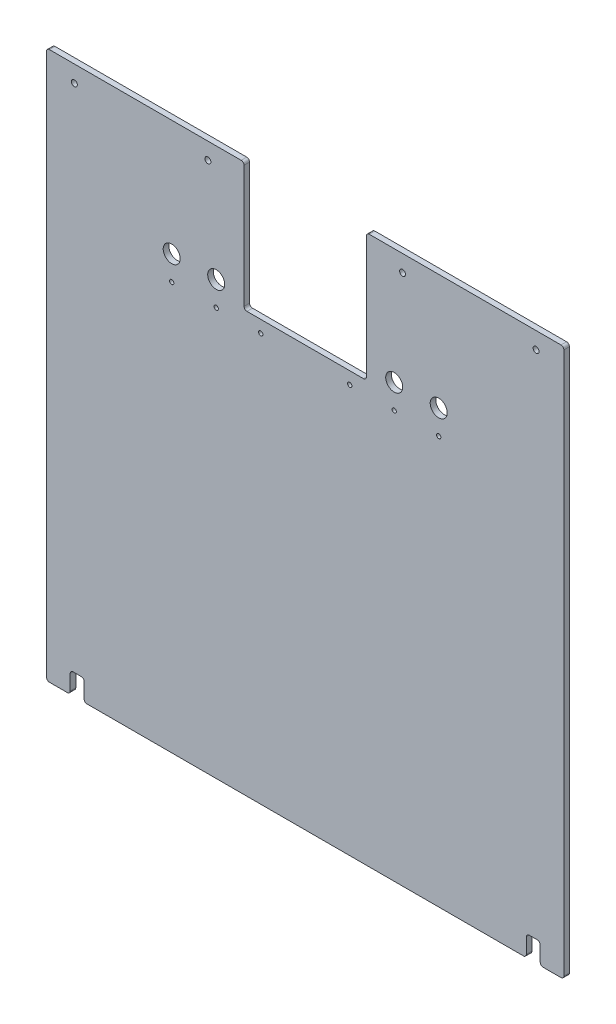
SolidWorks part; units mm, degrees
material "PC High Viscosity"
ref_plane "Front Plane" through (0, 0, 0) normal (0, 0, 1) x (1, 0, 0)
ref_plane "Top Plane" through (0, 0, 0) normal (0, 1, 0) x (1, 0, 0)
ref_plane "Right Plane" through (0, 0, 0) normal (1, 0, 0) x (0, 0, -1)
sketch "Sketch1" plane through (0, 0, 0) normal (0, 0, 1) x (1, 0, 0)
  line L1 (0, 0) -> (590.55, 0)
  line L2 (0, 0) -> (0, 479.425)
  line L3 (0, 479.425) -> (590.55, 479.425)
  line L4 (590.55, 0) -> (590.55, 479.425)
  dimension "D1" = 479.425
  dimension "D2" = 590.55
extrude "Boss-Extrude1" add sketch "Sketch1" along normal blind 6.35
sketch "Sketch2" plane through (0, 0, 6.35) normal (0, 0, 1) x (1, 0, 0)
  line L0 (0, 0) -> (590.55, 0) construction
  line L1 (31.75, 0) -> (38.1, 0) construction
  line L2 (31.75, 0) -> (31.75, 19.05) construction
  line L3 (31.75, 19.05) -> (38.1, 19.05) construction
  line L4 (38.1, 0) -> (38.1, 19.05) construction
  line L5 (295.275, 0) -> (295.275, 479.425) construction
  line L6 (590.55, 479.425) -> (0, 479.425) construction
  line L7 (552.45, 0) -> (552.45, 19.05) construction
  line L8 (558.8, 19.05) -> (552.45, 19.05) construction
  line L9 (558.8, 0) -> (558.8, 19.05) construction
  line L10 (558.8, 0) -> (552.45, 0) construction
  line L11 (26.9875, 0) -> (26.9875, 23.8125)
  line L12 (26.9875, 23.8125) -> (42.8625, 23.8125)
  line L13 (42.8625, 0) -> (42.8625, 23.8125)
  line L14 (42.8625, 0) -> (26.9875, 0)
  line L15 (563.5625, 23.8125) -> (547.6875, 23.8125)
  line L16 (563.5625, 0) -> (563.5625, 23.8125)
  line L17 (547.6875, 0) -> (547.6875, 23.8125)
  line L18 (547.6875, 0) -> (563.5625, 0)
  dimension "D1" = 6.35
  dimension "D2" = 527.05
  dimension "D3" = 19.05
  dimension "D4" = 4.7625
extrude "Cut-Extrude1" cut sketch "Sketch2" against normal through all
hole_wizard "#10 (0.1935) Diameter Hole1" positions "Sketch3" profile "Sketch4" hole size "#10" standard "ANSI Inch" end condition through all
sketch "Sketch3" plane through (0, 0, 6.35) normal (0, 0, 1) x (1, 0, 0)
  line L0 (295.275, 479.425) -> (295.275, 0) construction
  line L1 (590.55, 479.425) -> (0, 479.425) construction
  line L2 (42.8625, 0) -> (547.6875, 0) construction
  point P0 (142.875, 465.5078)
  point P2 (244.475, 465.5078)
  point P11 (346.075, 465.5078)
  point P12 (447.675, 465.5078)
  point P13 (193.675, 465.5078)
  point P18 (396.875, 465.5078)
  dimension "D1" = 101.6
  dimension "D2" = 101.6
  dimension "D3" = 13.9172
  dimension "D4" = 50.8
sketch "Sketch4" plane through (142.875, 465.5078, 6.35) normal (1, 0, 0) x (0, -1, 0)
  line L0 (0, 0) -> (0, 6.35)
  line L1 (0, 6.35) -> (2.4574, 6.35)
  line L2 (2.4574, 6.35) -> (2.4574, 0)
  line L5 (2.4574, 0) -> (0, 0)
  line L11 (0, -6.35) -> (0, 107.95) construction
  dimension "Thru Hole Dia." = 4.9149
  dimension "Thru Hole Depth" = 6.35
sketch "Sketch6" plane through (0, 0, 6.35) normal (0, 0, 1) x (1, 0, 0)
  line L0 (590.55, 479.425) -> (0, 479.425) construction
  line L1 (263.525, 479.425) -> (327.025, 479.425) construction
  line L2 (263.525, 479.425) -> (263.525, 809.625) construction
  line L3 (263.525, 809.625) -> (327.025, 809.625) construction
  line L4 (327.025, 479.425) -> (327.025, 809.625) construction
  line L5 (295.275, 479.425) -> (295.275, 809.625) construction
  line L6 (590.55, 625.475) -> (365.125, 625.475)
  line L7 (0, 479.425) -> (225.425, 479.425)
  line L8 (0, 479.425) -> (0, 625.475)
  line L9 (0, 625.475) -> (225.425, 625.475)
  line L10 (225.425, 479.425) -> (225.425, 625.475)
  line L11 (365.125, 479.425) -> (365.125, 625.475)
  line L12 (590.55, 479.425) -> (365.125, 479.425)
  line L13 (590.55, 479.425) -> (590.55, 625.475)
  line L14 (244.475, 465.5078) -> (244.475, 809.625) construction
  dimension "D1" = 63.5
  dimension "D2" = 330.2
  dimension "D3" = 146.05
  dimension "D4" = 19.05
extrude "Boss-Extrude3" add sketch "Sketch6" against normal up to surface (6.35 mm away) up to face at (145.3324, 465.5078, 0)
hole_wizard "49/64 (0.76563) Diameter Hole1" positions "Sketch7" profile "Sketch8" hole size "49/64" standard "ANSI Inch" end condition through all
sketch "Sketch7" plane through (0, 0, 6.35) normal (0, 0, 1) x (1, 0, 0)
  line L0 (142.875, 465.5078) -> (142.875, 493.3422) construction
  line L1 (365.125, 479.425) -> (225.425, 479.425) construction
  line L2 (365.125, 479.425) -> (225.425, 479.425) construction
  line L3 (295.275, 479.425) -> (295.275, 0) construction
  line L4 (42.8625, 0) -> (547.6875, 0) construction
  line L5 (193.675, 493.3422) -> (193.675, 465.5078) construction
  point P0 (142.875, 493.3422)
  point P13 (447.675, 493.3422)
  point P14 (193.675, 493.3422)
  point P17 (396.875, 493.3422)
sketch "Sketch8" plane through (142.875, 493.3422, 6.35) normal (1, 0, 0) x (0, -1, 0)
  line L0 (0, 0) -> (0, 6.35)
  line L1 (0, 6.35) -> (9.7235, 6.35)
  line L2 (9.7235, 6.35) -> (9.7235, 0)
  line L5 (9.7235, 0) -> (0, 0)
  line L11 (0, -6.35) -> (0, 107.95) construction
  dimension "Thru Hole Dia." = 19.447
  dimension "Thru Hole Depth" = 6.35
hole_wizard "1/4 Clearance Hole1" positions "Sketch9" profile "Sketch10" hole size "1/4" standard "ANSI Inch" end condition through all
sketch "Sketch9" plane through (0, 0, 6.35) normal (0, 0, 1) x (1, 0, 0)
  line L0 (295.275, 479.425) -> (295.275, 0) construction
  line L1 (365.125, 479.425) -> (225.425, 479.425) construction
  line L2 (42.8625, 0) -> (547.6875, 0) construction
  line L3 (0, 606.425) -> (225.425, 606.425) construction
  line L4 (0, 625.475) -> (0, 0) construction
  line L5 (225.425, 479.425) -> (225.425, 625.475) construction
  line L6 (225.425, 625.475) -> (0, 625.475) construction
  point P0 (31.75, 606.425)
  point P2 (184.15, 606.425)
  point P14 (406.4, 606.425)
  point P15 (558.8, 606.425)
  dimension "D1" = 19.05
  dimension "D2" = 31.75
  dimension "D3" = 152.4
sketch "Sketch10" plane through (31.75, 606.425, 6.35) normal (1, 0, 0) x (0, -1, 0)
  line L0 (0, 0) -> (0, 6.35)
  line L1 (0, 6.35) -> (3.3782, 6.35)
  line L2 (3.3782, 6.35) -> (3.3782, 0)
  line L5 (3.3782, 0) -> (0, 0)
  line L11 (0, -6.35) -> (0, 107.95) construction
  dimension "Thru Hole Dia." = 6.7564
  dimension "Thru Hole Depth" = 6.35
fillet "Fillet1" radius 3.302 16 edges at (26.9875, 23.8125, 3.175) (42.8625, 23.8125, 3.175) (42.8625, 0, 3.175) (547.6875, 0, 3.175) (547.6875, 23.8125, 3.175) (563.5625, 23.8125, 3.175) (563.5625, 0, 3.175) (590.55, 0, 3.175) (590.55, 625.475, 3.175) (365.125, 625.475, 3.175) (365.125, 479.425, 3.175) (225.425, 479.425, 3.175) (225.425, 625.475, 3.175) (0, 625.475, 3.175) (0, 0, 3.175) (26.9875, 0, 3.175)
equation "\"D3@Sketch6\"=1.75+4"
